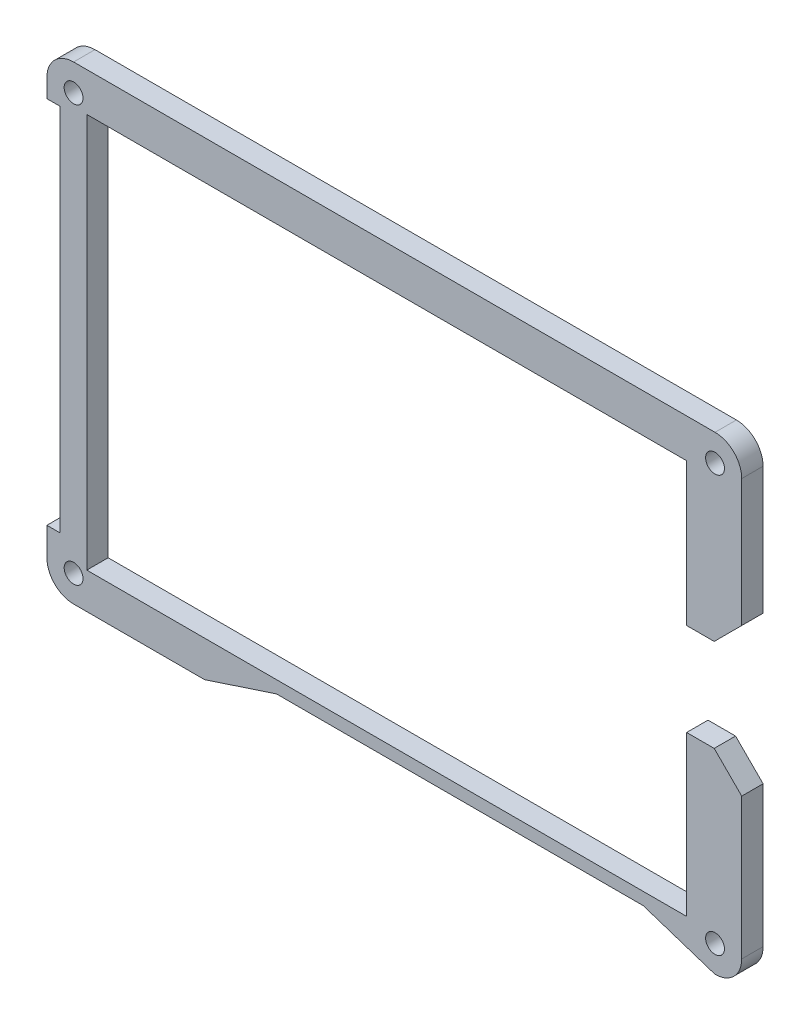
SolidWorks part; units mm, degrees
ref_plane "Front Plane" through (0, 0, 0) normal (0, 0, 1) x (1, 0, 0)
ref_plane "Top Plane" through (0, 0, 0) normal (0, 1, 0) x (1, 0, 0)
ref_plane "Right Plane" through (0, 0, 0) normal (1, 0, 0) x (0, 0, -1)
sketch "Sketch1" plane through (0, 0, 0) normal (0, 0, 1) x (1, 0, 0)
  line L0 (-401.0571, 148.341) -> (-380.1672, 148.341)
  line L1 (-399.1521, 148.341) -> (-399.1521, 95.6449)
  line L2 (-395.3675, 92.9525) -> (-395.3675, 149.2432)
  line L3 (-395.3675, 149.2432) -> (-309.8086, 149.2432)
  line L4 (-395.3675, 92.9525) -> (-309.8086, 92.9525)
  line L5 (-309.8086, 149.2432) -> (-309.8086, 92.9525)
  line L6 (-309.8086, 128.8851) -> (-321.2743, 128.8851)
  line L7 (-321.2743, 128.8851) -> (-321.2743, 115.6771)
  line L8 (-321.2743, 115.6771) -> (-309.8086, 115.6771)
  line L9 (-309.8086, 128.8851) -> (-305.8779, 128.8851)
  line L10 (-375.4172, 95.6449) -> (-401.0571, 95.6449)
  line L11 (-401.0571, 150.9566) -> (-401.0571, 148.341) construction
  line L12 (-305.7573, 154.7804) -> (-397.2471, 154.7804) construction
  line L13 (-301.9473, 91.6317) -> (-301.9473, 150.9704) construction
  line L14 (-315.9973, 91.1883) -> (-305.7573, 87.8217) construction
  line L15 (-315.9973, 91.1883) -> (-368.3165, 91.1883) construction
  line L16 (-368.3165, 91.1883) -> (-378.5565, 87.8217) construction
  line L17 (-378.5565, 87.8217) -> (-397.2472, 87.8217) construction
  line L18 (-401.0571, 95.6449) -> (-401.0571, 91.6593) construction
  line L19 (-401.0571, 150.9566) -> (-401.0571, 148.341)
  line L20 (-305.7573, 154.7804) -> (-397.2471, 154.7804)
  line L21 (-301.9473, 91.6317) -> (-301.9473, 150.9704)
  line L22 (-315.9973, 91.1883) -> (-305.7573, 87.8217)
  line L23 (-315.9973, 91.1883) -> (-368.3165, 91.1883)
  line L24 (-368.3165, 91.1883) -> (-378.5565, 87.8217)
  line L25 (-378.5565, 87.8217) -> (-397.2472, 87.8217)
  line L26 (-401.0571, 95.6449) -> (-401.0571, 91.6593)
  line L27 (-305.8779, 128.8851) -> (-301.9473, 132.8158)
  line L28 (-309.8086, 115.6771) -> (-305.8779, 115.6771)
  line L29 (-305.8779, 115.6771) -> (-301.9473, 111.7464)
  line L30 (-309.8086, 141.4927) -> (-301.9473, 141.4927) construction
  line L31 (-305.878, 141.4927) -> (-305.8779, 128.8851) construction
  arc A0 (-397.2471, 154.7804) -> (-401.0571, 150.9566) centre (-397.2471, 150.9704) ccw construction
  arc A1 (-301.9473, 150.9704) -> (-305.7573, 154.7804) centre (-305.7573, 150.9704) ccw construction
  arc A2 (-305.7573, 87.8217) -> (-301.9473, 91.6317) centre (-305.7573, 91.6317) ccw construction
  arc A3 (-401.0571, 91.6593) -> (-397.2472, 87.8217) centre (-397.2472, 91.6317) ccw construction
  arc A4 (-397.2471, 154.7804) -> (-401.0571, 150.9566) centre (-397.2471, 150.9704) ccw
  arc A5 (-301.9473, 150.9704) -> (-305.7573, 154.7804) centre (-305.7573, 150.9704) ccw
  arc A6 (-305.7573, 87.8217) -> (-301.9473, 91.6317) centre (-305.7573, 91.6317) ccw
  arc A7 (-401.0571, 91.6593) -> (-397.2472, 87.8217) centre (-397.2472, 91.6317) ccw
  circle A8 centre (-397.2471, 150.9704) radius 1.3462 construction
  circle A9 centre (-305.7573, 150.9704) radius 1.3462 construction
  circle A10 centre (-305.7573, 91.6317) radius 1.3462 construction
  circle A11 centre (-397.2472, 91.6317) radius 1.3462 construction
  circle A12 centre (-397.2471, 150.9704) radius 1.3462
  circle A13 centre (-305.7573, 150.9704) radius 1.3462
  circle A14 centre (-305.7573, 91.6317) radius 1.3462
  circle A15 centre (-397.2472, 91.6317) radius 1.3462
  dimension "D1" = 1.905
  dimension "D2" = 5.6896
  dimension "D3" = 5.5372
  dimension "D4" = 5.1308
  dimension "D5" = 7.8613
  dimension "D6" = 25.8953
  dimension "D7" = 13.208
  dimension "D8" = 11.4657
  dimension "D9" = 45
  dimension "D10" = 45
extrude "Boss-Extrude1" add sketch "Sketch1" along normal blind 3.048 contours L21 A5 L20 A4 L19 L0 L2 L3 L5 L9 L27 A13 A12 | L10 L2 L0 L1 | L26 A7 L25 L24 L23 L22 A6 L21 L29 L28 L5 L4 L2 L10 A15 A14 region at (-400.0327, 149.6488, 0) region at (-397.2598, 121.993, 0) region at (-397.2598, 94.6154, 0)
